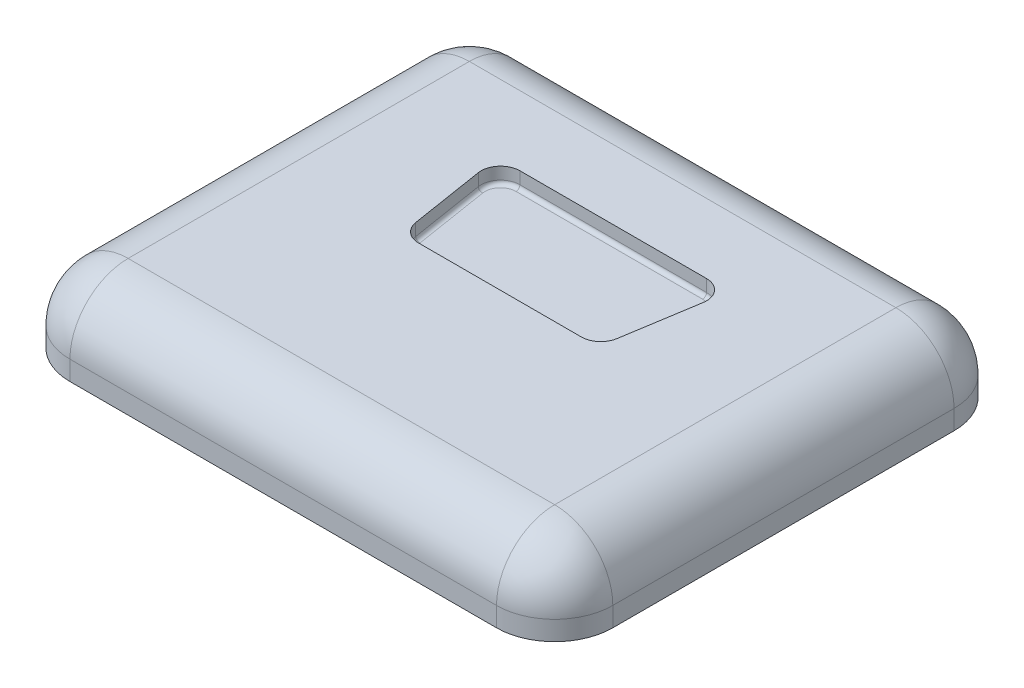
SolidWorks part; units mm, degrees
ref_plane "Front Plane" through (0, 0, 0) normal (0, 0, 1) x (1, 0, 0)
ref_plane "Top Plane" through (0, 0, 0) normal (0, 1, 0) x (1, 0, 0)
ref_plane "Right Plane" through (0, 0, 0) normal (1, 0, 0) x (0, 0, -1)
sketch "Sketch1" plane through (0, 0, 0) normal (0, 1, 0) x (1, 0, 0)
  line L1 (-112.56, 82.94) -> (167.44, 82.94)
  line L2 (-112.56, 82.94) -> (-112.56, -153.06)
  line L3 (-112.56, -153.06) -> (167.44, -153.06)
  line L4 (167.44, 82.94) -> (167.44, -153.06)
  dimension "D1" = 280
  dimension "D2" = 236
extrude "Boss-Extrude1" add sketch "Sketch1" along normal blind 40 contours L1 L4 L3 L2
fillet "Fillet1" radius 30 8 edges at (27.44, 40, -82.94) (167.44, 40, 35.06) (27.44, 40, 153.06) (-112.56, 40, 35.06) (167.44, 20, -82.94) (-112.56, 20, -82.94) (-112.56, 20, 153.06) (167.44, 20, 153.06)
sketch "Sketch3" plane through (0, 40, 0) normal (0, 1, 0) x (1, 0, 0)
  line L0 (27.44, -41.26) -> (27.44, 17.14) construction
  line L1 (-20.6848, 17.14) -> (75.5648, 17.14)
  line L2 (-30.56, 5.5649) -> (-24.4352, -32.8351)
  line L3 (-14.56, -41.26) -> (69.44, -41.26)
  line L4 (85.44, 5.5649) -> (79.3152, -32.8351)
  line L5 (27.44, 52.94) -> (27.44, -124.0364) construction
  line L6 (137.44, 52.94) -> (-82.56, 52.94) construction
  line L7 (-82.56, 82.94) -> (137.44, 82.94) construction
  arc A0 (-24.4352, -32.8351) -> (-14.56, -41.26) centre (-14.56, -31.26) ccw
  arc A1 (69.44, -41.26) -> (79.3152, -32.8351) centre (69.44, -31.26) ccw
  arc A2 (75.5648, 17.14) -> (85.44, 5.5649) centre (75.5648, 7.14) cw
  arc A3 (-20.6848, 17.14) -> (-30.56, 5.5649) centre (-20.6848, 7.14) ccw
  point P6 (-23.0914, -41.26)
  point P9 (77.9714, -41.26)
  point P12 (87.2862, 17.14)
  point P15 (-32.4062, 17.14)
  dimension "D3" = 10
  dimension "D1" = 84
  dimension "D2" = 116
  dimension "D4" = 58.4
  dimension "D5" = 65.8
extrude "Cut-Extrude2" cut sketch "Sketch3" against normal blind 8.25
fillet "Fillet2" radius 2 8 edges at (-27.4976, 31.75, 13.6351) (-28.2924, 31.75, -13.6303) (27.44, 31.75, -17.14) (83.1724, 31.75, -13.6303) (82.3776, 31.75, 13.6351) (75.9303, 31.75, 38.8676) (27.44, 31.75, 41.26) (-21.0503, 31.75, 38.8676)
